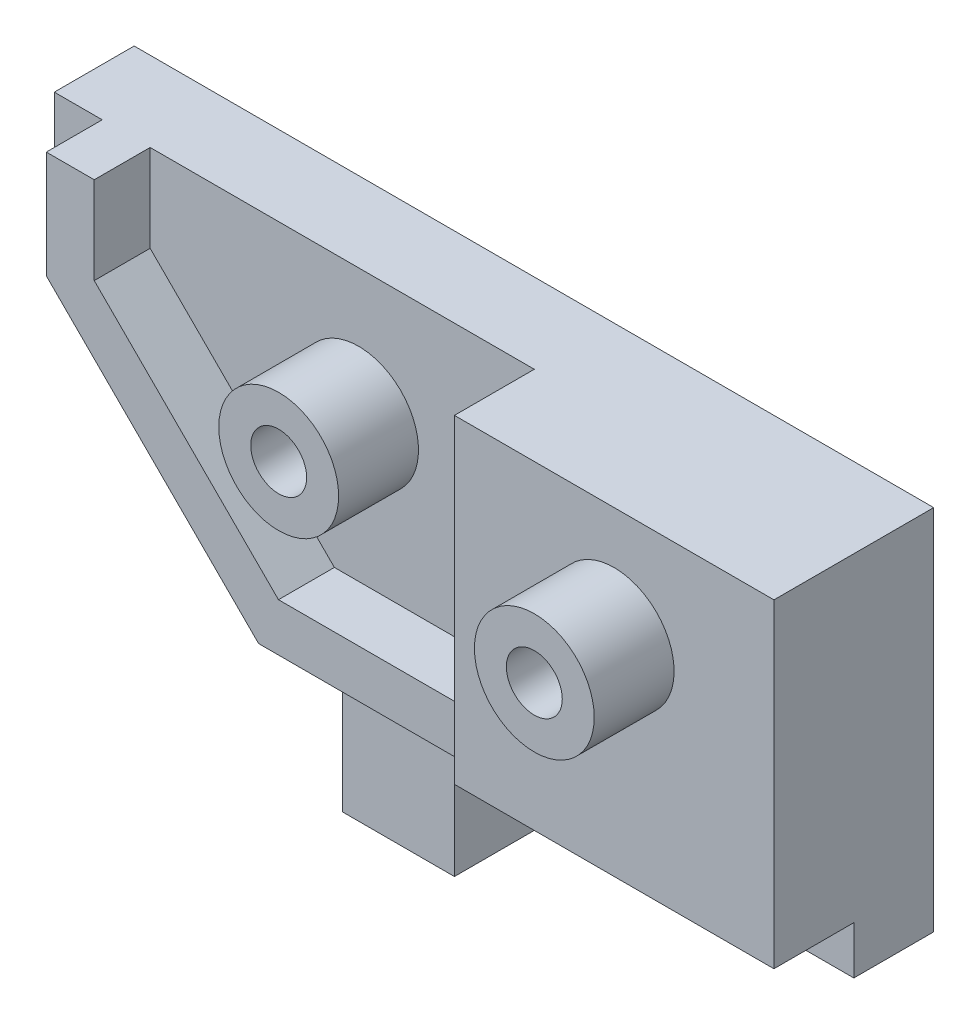
SolidWorks part; units mm, degrees
ref_plane "Front Plane" through (0, 0, 0) normal (0, 0, 1) x (1, 0, 0)
ref_plane "Top Plane" through (0, 0, 0) normal (0, 1, 0) x (1, 0, 0)
ref_plane "Right Plane" through (0, 0, 0) normal (1, 0, 0) x (0, 0, -1)
sketch "Sketch1" plane through (0, 0, 0) normal (0, 1, 0) x (1, 0, 0)
  line L0 (18, 0) -> (22, 0)
  line L1 (0, 0) -> (18, 0)
  line L2 (0, 0) -> (0, -5)
  line L3 (0, -5) -> (15, -5)
  line L4 (18, 0) -> (18, -10) construction
  line L6 (15, -5) -> (15, -10)
  line L7 (15, -10) -> (35, -10)
  line L8 (35, -5) -> (35, -10)
  line L10 (35, -5) -> (35, 0)
  line L11 (35, 0) -> (22, 0)
  dimension "D1" = 5
  dimension "D2" = 18
  dimension "D3" = 5
  dimension "D4" = 20
  dimension "D5" = 15
extrude "Boss-Extrude1" add sketch "Sketch1" along normal blind 23
sketch "Sketch2" plane through (0, 0, 10) normal (0, 0, 1) x (1, 0, 0)
  line L0 (35, 16) -> (25, 16) construction
  line L1 (35, 23) -> (35, 0) construction
  line L2 (15, 0) -> (35, 0) construction
  line L3 (0, 23) -> (0, 0) construction
  line L4 (0, 0) -> (15, 0) construction
  circle A0 centre (4, 15) radius 1.75
  circle A1 centre (25, 16) radius 1.75
  dimension "D5" = 3.5
  dimension "D6" = 3.5
  dimension "D1" = 10
  dimension "D2" = 16
  dimension "D3" = 4
  dimension "D4" = 15
extrude "Cut-Extrude1" cut sketch "Sketch2" against normal blind 10
sketch "Sketch3" plane through (0, 0, 0) normal (0, -1, 0) x (1, 0, 0)
  line L0 (0, 2.5) -> (35, 2.5) construction
  line L1 (25, 0) -> (25, 10) construction
  line L2 (35, 0) -> (0, 0) construction
  line L3 (15, 10) -> (35, 10) construction
  line L4 (0, 0) -> (0, 5) construction
  line L5 (35, 10) -> (35, 0) construction
  circle A1 centre (25, 2.5) radius 1.75
  point P1 (25, 10)
  dimension "D1" = 3.5
sketch "Sketch4" plane through (0, 0, 0) normal (0, -1, 0) x (1, 0, 0)
  line L0 (0, 2.5) -> (35, 2.5) construction
  line L1 (0, 0) -> (0, 5) construction
  line L3 (35, 10) -> (35, 0) construction
  line L7 (10, 0) -> (3, 0)
  line L8 (10, 0) -> (10, 5)
  line L9 (10, 5) -> (3, 5)
  line L10 (3, 0) -> (3, 5)
  line L11 (10, 0) -> (3, 5) construction
  line L12 (10, 5) -> (3, 0) construction
  line L17 (0, 5) -> (15, 5) construction
  point P12 (6.5, 2.5)
  dimension "D2" = 7
  dimension "D3" = 3
extrude "Boss-Extrude2" add sketch "Sketch4" along normal blind 7
sketch "Sketch6" plane through (0, 0, 5) normal (0, 0, 1) x (1, 0, 0)
  circle A0 centre (4, 15) radius 1.75
  circle A1 centre (4, 15) radius 3.75
  dimension "D1" = 2
  dimension "D2" = 3.5
extrude "Boss-Extrude3" add sketch "Sketch6" along normal blind 5
sketch "Sketch7" plane through (0, 0, 10) normal (0, 0, 1) x (1, 0, 0)
  circle A0 centre (25, 16) radius 1.75
  circle A1 centre (25, 16) radius 3.75
  dimension "D1" = 3.5
  dimension "D2" = 2
extrude "Boss-Extrude4" add sketch "Sketch7" along normal blind 5 contours A1 | A0
sketch "Sketch10" plane through (0, 0, 5) normal (0, 0, 1) x (1, 0, 0)
  line L0 (0, 23) -> (-15.0472, 23)
  line L1 (-15.0472, 15.0472) -> (0, 0)
  line L2 (0, 23) -> (0, 0) construction
  line L3 (-15.0472, 23) -> (-15.0472, 15.0472)
  line L4 (0, 23) -> (0, 0)
  dimension "D1" = 45
  dimension "D2" = 21.28
extrude "Boss-Extrude5" add sketch "Sketch10" against normal blind 5
sketch "Sketch11" plane through (0, 0, 5) normal (0, 0, 1) x (1, 0, 0)
  line L0 (-12.0472, 23) -> (-12.0472, 16.2899)
  line L1 (-15.0472, 23) -> (15, 23) construction
  line L2 (-12.0472, 16.2899) -> (1.2426, 3)
  line L3 (1.2426, 3) -> (15, 3)
  line L4 (15, 23) -> (15, 0) construction
  line L5 (-15.0472, 23) -> (-15.0472, 15.0472) construction
  line L6 (-15.0472, 15.0472) -> (0, 0) construction
  line L7 (0, 0) -> (3, 0) construction
  line L8 (-9.0472, 23) -> (-9.0472, 17.5325)
  line L9 (-9.0472, 17.5325) -> (2.4853, 6)
  line L10 (2.4853, 6) -> (15, 6)
  line L11 (-12.0472, 23) -> (-9.0472, 23)
  line L12 (15, 6) -> (15, 3)
  dimension "D1" = 3
  dimension "D2" = 3
  dimension "D3" = 3
  dimension "D4" = 3
extrude "Boss-Extrude6" add sketch "Sketch11" along normal blind 3.5
extrude "Cut-Extrude2" cut sketch "Sketch3" against normal blind 10 contours A1
sketch "Sketch12" plane through (15, 0, 0) normal (-1, 0, 0) x (0, 0, 1)
  line L1 (5, 3) -> (10, 3)
  line L2 (5, 3) -> (5, 0)
  line L3 (5, 0) -> (10, 0)
  line L4 (10, 3) -> (10, 0)
extrude "Cut-Extrude3" cut sketch "Sketch12" against normal up to surface (20 mm away) up to face at (35, 11.5, 5)
sketch "Sketch13" plane through (0, 0, 0) normal (0, 0, -1) x (-1, 0, 0)
  circle A0 centre (-25, 16) radius 2.5
  circle A1 centre (-4, 15) radius 2.5
  dimension "D1" = 5
  dimension "D2" = 5
extrude "Cut-Extrude4" cut sketch "Sketch13" against normal blind 4
